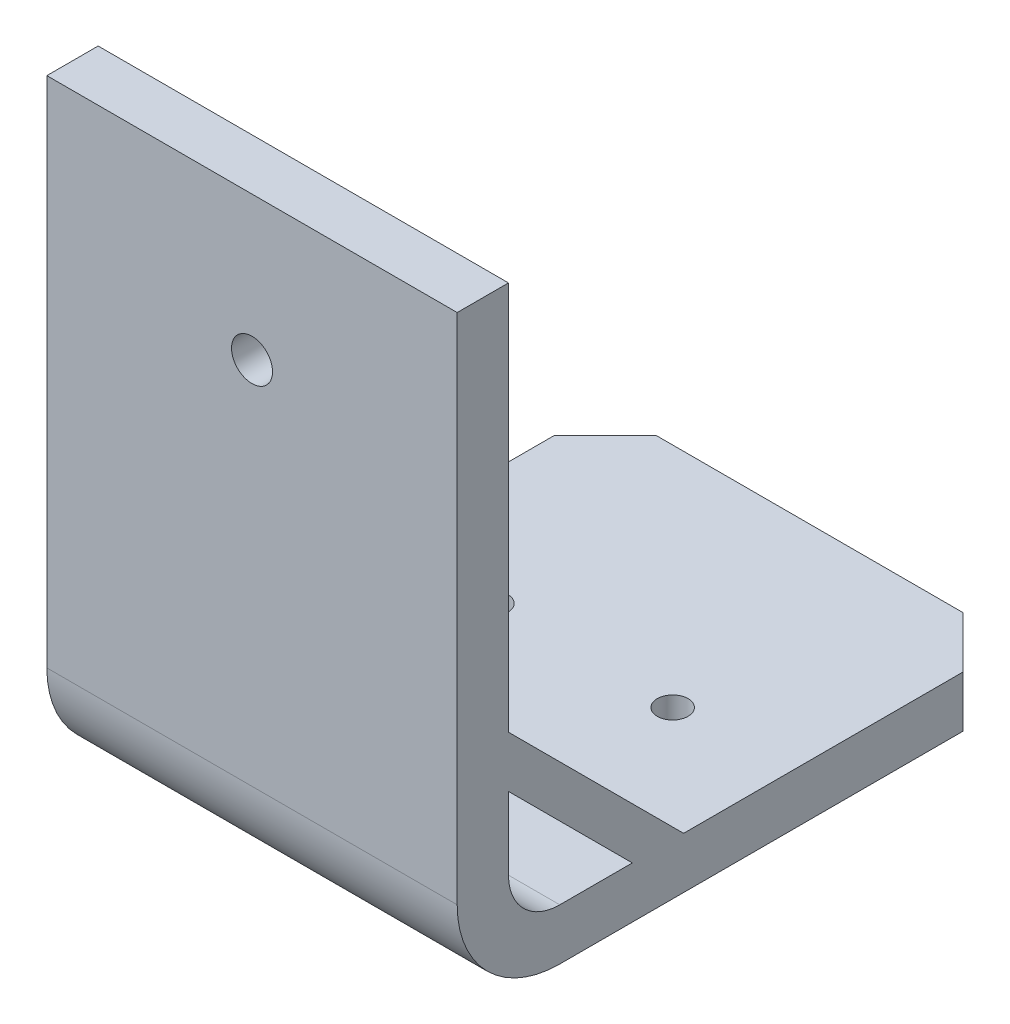
SolidWorks part; units mm, degrees
ref_plane "Front Plane" through (0, 0, 0) normal (0, 0, 1) x (1, 0, 0)
ref_plane "Top Plane" through (0, 0, 0) normal (0, 1, 0) x (1, 0, 0)
ref_plane "Right Plane" through (0, 0, 0) normal (1, 0, 0) x (0, 0, -1)
sketch "Sketch1" plane through (0, 0, 0) normal (0, 1, 0) x (1, 0, 0)
  line L0 (0, 0) -> (8.7882, 9.7647) construction
  line L1 (-14.9444, 22.1604) -> (14.9444, 22.1604)
  line L2 (-19.9444, 17.1604) -> (-19.9444, -22.1604)
  line L3 (-19.9444, -22.1604) -> (19.9444, -22.1604)
  line L4 (19.9444, 17.1604) -> (19.9444, -22.1604)
  line L5 (-17.576, 19.5289) -> (19.9444, -22.1604) construction
  line L6 (-19.9444, -22.1604) -> (17.576, 19.5289) construction
  line L7 (8.7882, 9.7647) -> (8.7882, -9.7647) construction
  line L8 (14.9444, 22.1604) -> (19.9444, 17.1604)
  line L9 (-14.9444, 22.1604) -> (-19.9444, 17.1604)
  line L10 (8.7882, -9.7647) -> (8.7882, 0) construction
  line L11 (8.7882, 9.7647) -> (-8.7882, 9.7647) construction
  line L12 (-8.7882, 9.7647) -> (-8.7882, -9.7647) construction
  line L13 (-8.7882, -9.7647) -> (-8.7882, 0) construction
  circle A0 centre (8.7882, 0) radius 1.5
  circle A1 centre (-8.7882, 0) radius 1.5
  point P0 (0, 0)
  dimension "D2" = 3
  dimension "D3" = 3
  dimension "D1" = 13.137
  dimension "D4" = 17.5764
  dimension "D5" = 39.8888
  dimension "D6" = 44.3209
extrude "Boss-Extrude1" add sketch "Sketch1" along normal blind 5 contours L1 L8 L4 L3 L2 L9
sketch "Sketch2" plane through (0, 0, 0) normal (0, -1, 0) x (1, 0, 0)
  line L0 (-8.7807, 0) -> (0, 0) construction
  line L1 (8.7882, 0) -> (0, 0) construction
  circle A0 centre (-8.7807, 0) radius 1.5
  circle A1 centre (8.7882, 0) radius 1.5
extrude "Cut-Extrude1" cut sketch "Sketch2" against normal blind 5 contours A0
extrude "Cut-Extrude3" cut sketch "Sketch1<4>" along normal through all from offset 0 flip side to cut
sketch "Sketch1<4>" plane through (0, 0, 0) normal (0, 1, 0) x (1, 0, 0) same geometry as "Sketch1"
sketch "Sketch4" plane through (19.9444, 0, 0) normal (1, 0, 0) x (0, 0, -1)
  line L1 (-22.1604, 5) -> (-22.1604, 0)
  line L2 (-27.1604, 10) -> (-32.1604, 10)
  arc A0 (-32.1604, 10) -> (-22.1604, 0) centre (-22.1604, 10) ccw
  arc A1 (-27.1604, 10) -> (-22.1604, 5) centre (-22.1604, 10) ccw
extrude "Boss-Extrude2" add sketch "Sketch4" against normal blind 40
sketch "Sketch5" plane through (19.9444, 0, 0) normal (1, 0, 0) x (0, 0, -1)
  line L0 (-27.1604, 10) -> (-27.1604, 60)
  line L1 (-32.1604, 10) -> (-32.1604, 60)
  line L2 (-32.1604, 60) -> (-27.1604, 60)
  line L3 (-32.1604, 10) -> (-27.1604, 10)
extrude "Boss-Extrude3" add sketch "Sketch5" against normal blind 40
sketch "Sketch6" plane through (19.9444, 0, 0) normal (1, 0, 0) x (0, 0, -1)
  line L1 (-18.6249, 13.5355) -> (-27.1604, 22.0711)
  line L2 (-27.1604, 10) -> (-27.1604, 60) construction
  line L3 (-27.1604, 22.0711) -> (-10.0894, 5)
  line L4 (17.1604, 5) -> (-22.1604, 5) construction
  line L5 (-27.1604, 22.0711) -> (-27.1604, 17.0711)
  line L6 (-10.0894, 5) -> (-15.0894, 5)
  line L7 (-27.1604, 17.0711) -> (-15.0894, 5)
  line M8 (17.1604, 5) -> (-22.1604, 5)
  line M10 (-27.1604, 10) -> (-27.1604, 60)
extrude "Boss-Extrude4" add sketch "Sketch6" against normal blind 40 contours L7 L3 L1 M10 M8 region at (19.9444, 12.357, 19.8034)
sketch "Sketch8" plane through (0, 0, 32.1604) normal (0, 0, 1) x (1, 0, 0)
  line L0 (-20.0556, 60) -> (19.9444, 60) construction
  line L1 (19.9444, 60) -> (-0.0556, 60) construction
  line L2 (-0.0556, 60) -> (-0.0556, 46) construction
sketch "Sketch9" plane through (0, 0, 32.1604) normal (0, 0, 1) x (1, 0, 0)
  circle A0 centre (-0.0556, 46) radius 2
extrude "Cut-Extrude4" cut sketch "Sketch9" against normal through all
